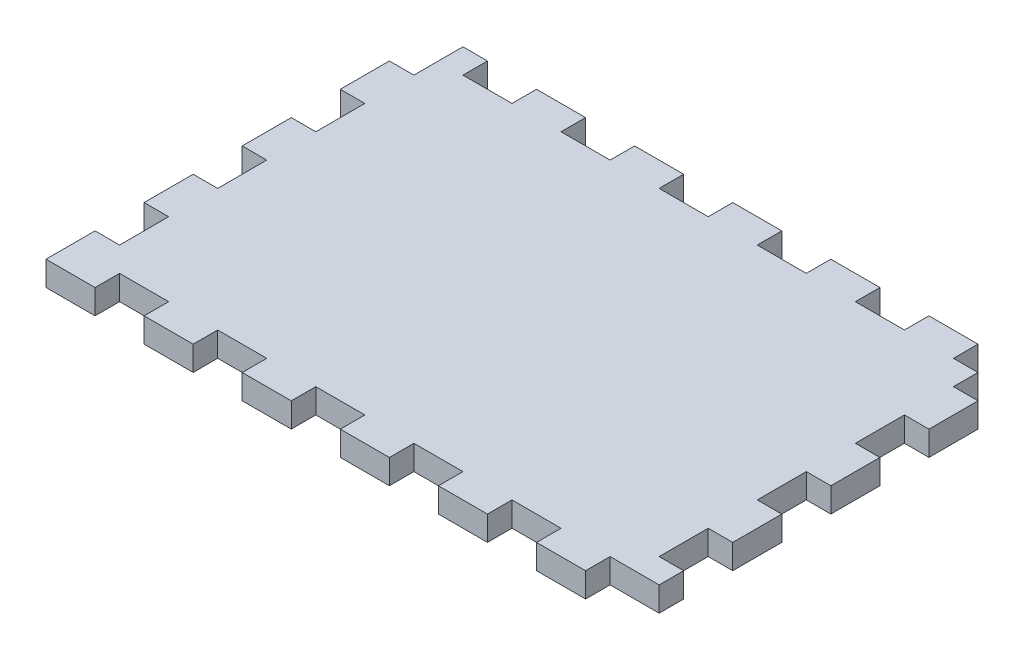
SolidWorks part; units mm, degrees
material "Acrylic (Medium-high impact)"
ref_plane "Front Plane" through (0, 0, 0) normal (0, 0, 1) x (1, 0, 0)
ref_plane "Top Plane" through (0, 0, 0) normal (0, 1, 0) x (1, 0, 0)
ref_plane "Right Plane" through (0, 0, 0) normal (1, 0, 0) x (0, 0, -1)
sketch "Sketch1" plane through (0, 0, 0) normal (0, 1, 0) x (1, 0, 0)
  line L1 (0, 0) -> (152.4, 0)
  line L2 (0, 0) -> (0, 101.6)
  line L3 (0, 101.6) -> (152.4, 101.6)
  line L4 (152.4, 0) -> (152.4, 101.6)
  dimension "D3" = 101.6
  dimension "D5" = 152.4
extrude "Boss-Extrude2" add sketch "Sketch1" along normal blind 6.35 contours L1 L4 L3 L2 region at (76.2, 0, -50.8)
ref_plane "Plane1" through (76.2, 0, 0) normal (-1, 0, 0) x (0, 0, 1)
ref_plane "Plane2" through (0, 0, -50.8) normal (0, 0, -1) x (-1, 0, 0)
sketch "Sketch2" plane through (0, 6.35, 0) normal (0, 1, 0) x (1, 0, 0)
  line L0 (6.35, 101.6) -> (6.35, 0)
  line L1 (12.7, 101.6) -> (12.7, 95.25)
  line L2 (0, 0) -> (152.4, 0) construction
  line L3 (0, 95.25) -> (152.4, 95.25)
  line L4 (25.4, 101.6) -> (25.4, 95.25)
  line L5 (152.4, 0) -> (152.4, 101.6) construction
  line L6 (0, 0) -> (0, 101.6) construction
  line L7 (0, 101.6) -> (152.4, 101.6) construction
  line L8 (0, 12.7) -> (6.35, 12.7)
  line L17 (0, 25.4) -> (6.35, 25.4)
  line L18 (0, 38.1) -> (6.35, 38.1)
  line L19 (0, 50.8) -> (6.35, 50.8)
  line L20 (0, 0) -> (152.4, 0)
  line L21 (152.4, 0) -> (152.4, 101.6)
  line L22 (152.4, 101.6) -> (0, 101.6)
  line L23 (0, 101.6) -> (0, 0)
  line L24 (0, 0) -> (152.4, 0)
  line L25 (152.4, 0) -> (152.4, 101.6)
  line L26 (152.4, 101.6) -> (0, 101.6)
  line L27 (0, 101.6) -> (0, 0)
  line L28 (0, 63.5) -> (6.35, 63.5)
  line L29 (0, 76.2) -> (6.35, 76.2)
  line L30 (0, 88.9) -> (6.35, 88.9)
  line L31 (0, 101.6) -> (6.35, 101.6)
  line L32 (38.1, 101.6) -> (38.1, 95.25)
  line L33 (50.8, 101.6) -> (50.8, 95.25)
  line L34 (63.5, 101.6) -> (63.5, 95.25)
  line L35 (76.2, 101.6) -> (76.2, 95.25)
  line L36 (88.9, 101.6) -> (88.9, 95.25)
  line L37 (101.6, 101.6) -> (101.6, 95.25)
  line L38 (114.3, 101.6) -> (114.3, 95.25)
  line L39 (127, 101.6) -> (127, 95.25)
  line L40 (139.7, 101.6) -> (139.7, 95.25)
  line L41 (152.4, 101.6) -> (152.4, 95.25)
  line L42 (165.1, 101.6) -> (165.1, 95.25)
  line M20 (152.4, 0) -> (152.4, 101.6)
  line M21 (152.4, 101.6) -> (0, 101.6)
  line M22 (0, 101.6) -> (0, 0)
  dimension "D1" = 6.35
  dimension "D2" = 6.35
  dimension "D4" = 12.7
  dimension "D6" = 12.7
  dimension "D7" = 12.7
  dimension "D3" = 0
  dimension "D5" = 8
extrude "Cut-Extrude2" cut sketch "Sketch2" against normal blind 6.35 contours L17 L8 L0 M22 | L19 L18 L0 M22 | L29 L27 L28 L0 | L3 L0 M22 M21 | L30 L0 L3 M22 region at (3.175, 6.35, -92.075) region at (3.175, 6.35, -69.85) region at (3.175, 6.35, -98.425) region at (3.175, 6.35, -44.45) region at (3.175, 6.35, -19.05)
mirror "Mirror1" about plane through (76.2, 0, 0) normal (-1, 0, 0) of "Cut-Extrude2"
extrude "Cut-Extrude3" cut sketch "Sketch2<4>" against normal blind 6.35 contours L4 L1 L3 M21 | L33 L26 L32 L3 | L35 L26 L34 L3 | L37 L26 L36 L3 | L39 L26 L38 L3 | L40 L3 M21 M20 region at (19.05, 6.35, -98.425) region at (44.45, 6.35, -98.425) region at (69.85, 6.35, -98.425) region at (95.25, 6.35, -98.425) region at (146.05, 6.35, -98.425) region at (120.65, 6.35, -98.425)
sketch "Sketch2<4>" plane through (0, 6.35, 0) normal (0, 1, 0) x (1, 0, 0) same geometry as "Sketch2"
mirror "Mirror2" about plane through (0, 0, -50.8) normal (0, 0, -1) of "Cut-Extrude3"
equation "\"acrillic thickness\"= 1 / 4"
equation "\"D1@Sketch2\"=\"acrillic thickness\""
equation "\"D2@Sketch2\"=\"acrillic thickness\""
